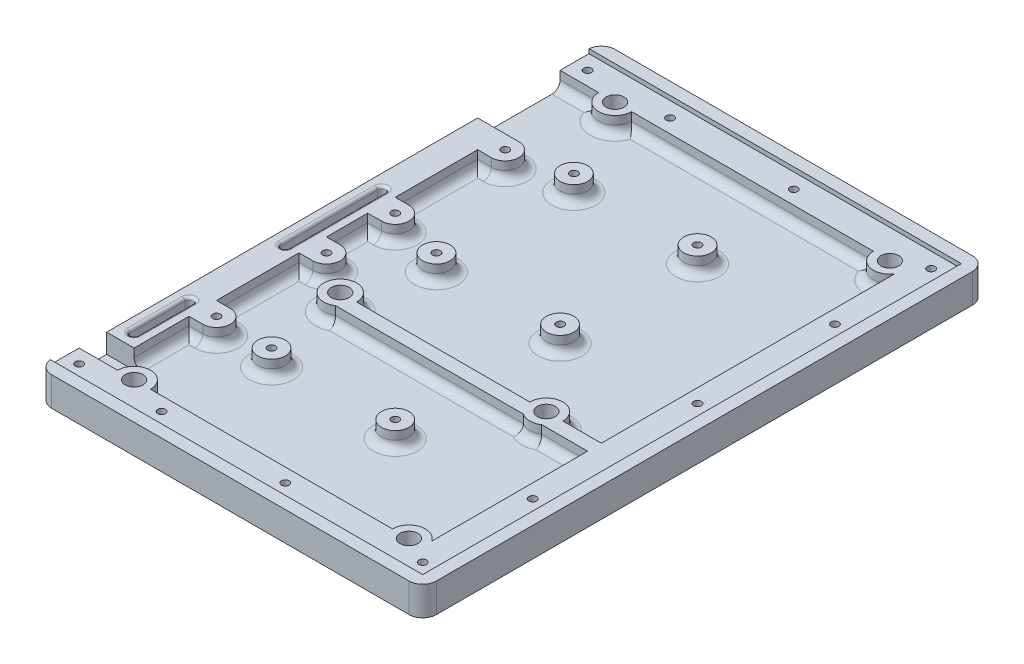
SolidWorks part; units mm, degrees
ref_plane "Front Plane" through (0, 0, 0) normal (0, 0, 1) x (1, 0, 0)
ref_plane "Top Plane" through (0, 0, 0) normal (0, 1, 0) x (1, 0, 0)
ref_plane "Right Plane" through (0, 0, 0) normal (1, 0, 0) x (0, 0, -1)
sketch "Sketch1" plane through (0, 0, 0) normal (0, 1, 0) x (1, 0, 0)
  line L1 (0, 0) -> (135, 0) construction
  line L2 (0, 0) -> (0, -195) construction
  line L3 (0, -195) -> (135, -195) construction
  line L4 (135, 0) -> (135, -195) construction
  line L8 (-0.5, 0.5) -> (-0.5, -195.5)
  line L9 (-0.5, -195.5) -> (135.5, -195.5)
  line L10 (135.5, 0.5) -> (135.5, -195.5)
  line L11 (-0.5, 0.5) -> (135.5, 0.5)
  line L13 (140, -200) -> (0, -200)
  line L14 (140, -200) -> (140, 5)
  line L15 (140, 5) -> (0, 5)
  line L16 (0, -200) -> (0, 5)
  dimension "D1" = 135
  dimension "D2" = 195
  dimension "D5" = 5
  dimension "D3" = 5
  dimension "D6" = 5
  dimension "D7" = 0
  dimension "D4" = 0.5
extrude "Boss-Extrude1" add sketch "Sketch1" along normal blind 1.6 contours L16 L13 L14 L15 L11 L10 L9 region at (2.4824, 0, -2.75)
sketch "Sketch2" plane through (0, 0, 0) normal (0, 1, 0) x (1, 0, 0)
  line L8 (0, 0) -> (135, 0) construction
  line L9 (10, -10) -> (125, -10)
  line L10 (10, -10) -> (10, -185)
  line L11 (10, -185) -> (125, -185)
  line L12 (125, -10) -> (125, -185)
  line L14 (0, -195) -> (135, -195) construction
  line L15 (0, 0) -> (0, -195) construction
  line L16 (-0.5, 0.5) -> (-0.5, -195.5) construction
  line L17 (140, 5) -> (0, 5)
  line L18 (140, 5) -> (140, -200)
  line L19 (140, -200) -> (0, -200)
  line L20 (0, 5) -> (0, -200)
  line L21 (-4.176, -185) -> (19.5, -185)
  line L22 (-4.176, -185) -> (-4.176, -175)
  line L23 (-4.176, -175) -> (19.5, -175)
  line L24 (19.5, -185) -> (19.5, -175)
  line L26 (-7.239, -10) -> (14.5, -10)
  line L27 (-7.239, -10) -> (-7.239, -40)
  line L28 (-7.239, -40) -> (14.5, -40)
  line L29 (14.5, -10) -> (14.5, -40)
  line L30 (129.7056, -120) -> (30, -120)
  line L31 (129.7056, -120) -> (129.7056, -125)
  line L32 (129.7056, -125) -> (30, -125)
  line L33 (30, -120) -> (30, -125)
  dimension "D1" = 10
  dimension "D2" = 10
  dimension "D3" = 10
  dimension "D4" = 10
  dimension "D5" = 10
  dimension "D6" = 20
  dimension "D7" = 10
  dimension "D8" = 30
  dimension "D9" = 15
  dimension "D10" = 70
  dimension "D11" = 5
  dimension "D12" = 30
extrude "Boss-Extrude2" add sketch "Sketch2" against normal blind 6 contours L31 L32 L12 L11 L21 L20 L19 L18 L17 L26 L9 L30 | L28 L20 L23 L10 | L30 L33 L32 L12 | L32 L31 L30 L12 region at (5, 0, 7.5176) region at (5, 0, 107.5) region at (127.3528, 0, 122.5) region at (77.5, 0, 122.5)
sketch "Sketch3" plane through (0, -6, 0) normal (0, -1, 0) x (1, 0, 0)
  line L1 (0, 200) -> (140, 200)
  line L2 (0, 200) -> (0, -5)
  line L3 (0, -5) -> (140, -5)
  line L4 (140, 200) -> (140, -5)
extrude "Boss-Extrude3" add sketch "Sketch3" along normal blind 3
sketch "Sketch4" plane through (0, 0, 0) normal (0, 1, 0) x (1, 0, 0)
  line L0 (0, 0) -> (135, 0) construction
  line L1 (0, -200) -> (0, 5) construction
  line L2 (135, 0) -> (135, -195) construction
  line L3 (0, -195) -> (135, -195) construction
  circle A0 centre (5, -5) radius 1.4
  circle A1 centre (35, -5) radius 1.4
  circle A2 centre (80, -5) radius 1.4
  circle A3 centre (130, -5) radius 1.4
  circle A4 centre (5, -190) radius 1.4
  circle A5 centre (35, -190) radius 1.4
  circle A6 centre (80, -190) radius 1.4
  circle A7 centre (130, -190) radius 1.4
  circle A8 centre (130, -40) radius 1.4
  circle A9 centre (130, -150) radius 1.4
  circle A10 centre (130, -90) radius 1.4
  dimension "D1" = 5
  dimension "D3" = 30
  dimension "D4" = 5
  dimension "D6" = 5
  dimension "D7" = 35
  dimension "D2" = 5
  dimension "D5" = 45
  dimension "D8" = 40
  dimension "D9" = 50
extrude "Cut-Extrude1" cut sketch "Sketch4" against normal up to surface (6 mm away) up to face at (48.3333, -6, 109.1667)
sketch "Sketch5" plane through (0, 0, 0) normal (0, 1, 0) x (1, 0, 0)
  line L0 (0, -200) -> (0, 5) construction
  line L1 (0, 0) -> (135, 0) construction
  line L3 (10, -40) -> (10, -175) construction
  line L4 (15, -40) -> (10, -40)
  line L5 (15, -40) -> (15, -50)
  line L6 (15, -50) -> (10, -50)
  line L7 (10, -40) -> (10, -50)
  line L8 (10, -40) -> (10, -175) construction
  line L9 (15, -80) -> (10, -80)
  line L10 (15, -80) -> (15, -90)
  line L11 (15, -90) -> (10, -90)
  line L12 (10, -80) -> (10, -90)
  line L13 (0, -10) -> (125, -10) construction
  line L14 (15, -115) -> (10, -115)
  line L15 (15, -115) -> (15, -105)
  line L16 (15, -105) -> (10, -105)
  line L17 (10, -115) -> (10, -105)
  line L18 (15, -155) -> (10, -155)
  line L19 (15, -155) -> (15, -145)
  line L20 (15, -145) -> (10, -145)
  line L21 (10, -155) -> (10, -145)
  line L22 (135, 0) -> (135, -195) construction
  line L23 (0, -185) -> (125, -185) construction
  circle A0 centre (35, -40) radius 1.4
  circle A4 centre (80, -40) radius 1.4
  circle A6 centre (35, -90) radius 1.4
  circle A7 centre (130, -90) radius 1.4 construction
  circle A8 centre (80, -90) radius 1.4
  circle A9 centre (35, -150) radius 1.4
  circle A11 centre (80, -150) radius 1.4
  circle A12 centre (15, -45) radius 1.4
  circle A13 centre (15, -85) radius 1.4
  circle A14 centre (15, -150) radius 1.4
  circle A15 centre (15, -110) radius 1.4
  circle A16 centre (35, -40) radius 5
  circle A17 centre (80, -40) radius 5
  circle A18 centre (15, -85) radius 5
  circle A19 centre (15, -45) radius 5
  circle A20 centre (15, -110) radius 5
  circle A21 centre (35, -90) radius 5
  circle A22 centre (80, -90) radius 5
  circle A23 centre (80, -150) radius 5
  circle A24 centre (35, -150) radius 5
  circle A25 centre (15, -150) radius 5
  circle A27 centre (20, -10) radius 6
  circle A28 centre (120, -10) radius 6
  circle A29 centre (120, -185) radius 6
  circle A30 centre (20, -185) radius 6
  circle A31 centre (105, -120) radius 6
  circle A32 centre (30, -120) radius 6
  dimension "D2" = 20
  dimension "D3" = 10
  dimension "D4" = 0
  dimension "D5" = 12
  dimension "D6" = 15
  dimension "D8" = 5
  dimension "D9" = 40
  dimension "D12" = 15
  dimension "D13" = 120
  dimension "D15" = 30
  dimension "D7" = 45
  dimension "D10" = 15
  dimension "D11" = 15
  dimension "D14" = 30
extrude "Boss-Extrude4" add sketch "Sketch5" against normal up to surface (6 mm away) contours A22 A8 | A17 A4 | A16 A0 | A21 A6 | A24 A9 | A23 A11 | A19 L4 L7 | L5 A19 A12 | A19 L7 L6 | L5 A19 A12 | A25 L21 L18 | L19 A25 A14 | L19 A25 A14 | A25 L20 L21 | L10 A18 A13 | L10 A18 A13 | A18 L12 L11 | A18 L9 L12 | A20 L16 L17 | L15 A20 A15 | A20 L17 L14 | L15 A20 A15 | A27 | A28 | A32 | A31 | A29 | A30 region at (11.1168, 0, 41.1168) region at (17.252, 0, 45) region at (12.748, 0, 45) region at (11.1168, 0, 48.8832) region at (11.1168, 0, 81.1168) region at (17.252, 0, 85) region at (12.748, 0, 85) region at (11.1168, 0, 88.8832) region at (12.748, 0, 110) region at (17.252, 0, 110) region at (11.1168, 0, 113.8832) region at (11.1168, 0, 106.1168) region at (12.748, 0, 150) region at (17.252, 0, 150) region at (11.1168, 0, 153.8832) region at (11.1168, 0, 146.1168) region at (30.1414, 0, 40) region at (75.1414, 0, 40) region at (30.1414, 0, 90) region at (75.1414, 0, 90) region at (75.1414, 0, 150) region at (30.1414, 0, 150) up to face at (48.3333, -6, 109.1667)
sketch "Sketch6" plane through (0, 0, 0) normal (0, 1, 0) x (1, 0, 0)
  line L0 (5, -150) -> (5, -170) construction
  line L5 (6.5, -150) -> (6.5, -170)
  line L6 (3.5, -150) -> (3.5, -170)
  line L7 (0, -200) -> (0, 5) construction
  line L8 (0, -195) -> (135, -195) construction
  line L9 (5, -80) -> (5, -115) construction
  line L10 (6.5, -80) -> (6.5, -115)
  line L11 (3.5, -80) -> (3.5, -115)
  line L12 (0, 0) -> (135, 0) construction
  arc A0 (6.5, -150) -> (3.5, -150) centre (5, -150) ccw
  arc A1 (3.5, -170) -> (6.5, -170) centre (5, -170) ccw
  arc A2 (6.5, -80) -> (3.5, -80) centre (5, -80) ccw
  arc A3 (3.5, -115) -> (6.5, -115) centre (5, -115) ccw
  point P2 (5, -160)
  point P13 (5, -97.5)
  dimension "D4" = 80
  dimension "D1" = 5
  dimension "D2" = 25
  dimension "D3" = 20
  dimension "D5" = 115
extrude "Cut-Extrude2" cut sketch "Sketch6" against normal blind 4
sketch "Sketch7" plane through (0, -6, 0) normal (0, 1, 0) x (1, 0, 0)
  line L0 (0, -185) -> (14, -185) construction
  line L1 (0, -175) -> (14, -175)
  line L2 (0, -175) -> (0, -185)
  line L3 (0, -185) -> (14, -185)
  line L4 (14, -175) -> (14, -185)
  dimension "D1" = 14
extrude "Cut-Extrude3" cut sketch "Sketch7" against normal blind 1
fillet "Fillet1" radius 3 37 edges at (70, -6, 185) (118, -6, 120) (125, -6, 153.3417) (116.6583, -6, 125) (125, -6, 66.6583) (7, -6, 10) (12.5, -6, 145) (20, -6, 150) (12.5, -6, 105) (20, -6, 110) (12.5, -6, 80) (20, -6, 85) (7.5, -6, 40) (20, -6, 45) (80, -6, 35) (80, -6, 85) (80, -6, 145) (35, -6, 145) (35, -6, 85) (35, -6, 35) (12.5, -6, 155) (10, -6, 165) (10, -6, 130) (12.5, -6, 115) (10, -6, 97.5) (12.5, -6, 90) (10, -6, 65) (12.5, -6, 50) (118.2679, -6, 179.2554) (20, -6, 16) (118.2679, -6, 15.7446) (70, -6, 10) (105, -6, 114) (67.5, -6, 120) (24.7132, -6, 117.1627) (105, -6, 126) (67.5, -6, 125)
fillet "Fillet2" radius 1 8 edges at (6.5, 0, 160) (5, 0, 171.5) (3.5, 0, 160) (6.5, 0, 97.5) (5, 0, 116.5) (3.5, 0, 97.5) (5, 0, 148.5) (5, 0, 78.5)
fillet "Fillet3" radius 5 4 edges at (140, -3.7, -5) (140, -3.7, 200) (0, -3.7, 200) (0, -3.7, -5)
sketch "Sketch8" plane through (0, 0, 0) normal (0, 1, 0) x (1, 0, 0)
  line L0 (0, -195) -> (135, -195) construction
  circle A0 centre (20, -10) radius 3.25
  circle A1 centre (30, -120) radius 3.25
  circle A2 centre (105, -120) radius 3.25
  circle A3 centre (120, -10) radius 3.25
  circle A4 centre (20, -185) radius 3.25
  circle A5 centre (120, -185) radius 3.25
  dimension "D1" = 10
extrude "Cut-Extrude4" cut sketch "Sketch8" against normal through all
